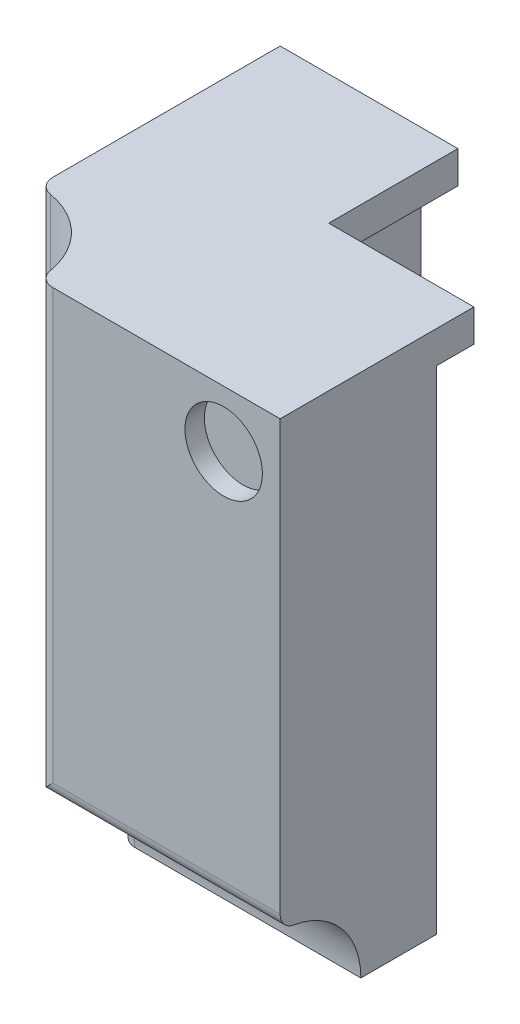
SolidWorks part; units mm, degrees
ref_plane "Front Plane" through (0, 0, 0) normal (0, 0, 1) x (1, 0, 0)
ref_plane "Top Plane" through (0, 0, 0) normal (0, 1, 0) x (1, 0, 0)
ref_plane "Right Plane" through (0, 0, 0) normal (1, 0, 0) x (0, 0, -1)
sketch "Sketch1" plane through (0, 0, 0) normal (0, 1, 0) x (1, 0, 0)
  line L0 (0, 0) -> (50.8, 0)
  line L1 (50.8, 0) -> (50.8, 24.638)
  line L2 (50.8, 24.638) -> (22.1234, 24.638)
  line L3 (22.1234, 24.638) -> (22.1234, 50.8)
  line L4 (22.1234, 50.8) -> (0, 50.8)
  line L5 (0, 50.8) -> (0, 0)
  dimension "D1" = 50.8
  dimension "D2" = 24.638
  dimension "D3" = 22.1234
  dimension "D4" = 50.8
extrude "Boss-Extrude1" add sketch "Sketch1" along normal blind 82.55 contours L0 L1 L2 L3 L4 L5
sketch "Sketch2" plane through (50.8, 0, 0) normal (1, 0, 0) x (0, 0, -1)
  line L0 (0, 82.55) -> (0, 0) construction
  line L1 (0, 0) -> (24.638, 0) construction
  line L2 (12.7, 0) -> (0, 0)
  line L3 (0, 0) -> (0, 12.7)
  arc A0 (0, 12.7) -> (12.7, 0) centre (0, 0) cw
  dimension "D1" = 12.7
extrude "Cut-Extrude1" cut sketch "Sketch2" against normal blind 76.2 contours A0 L2 L3
sketch "Sketch3" plane through (0, 0, -50.8) normal (0, 0, -1) x (-1, 0, 0)
  line L0 (0, 82.55) -> (0, 0) construction
  line L1 (-22.1234, 0) -> (0, 0) construction
  line L2 (-12.7, 0) -> (0, 0)
  line L3 (0, 0) -> (0, 12.7)
  arc A0 (0, 12.7) -> (-12.7, 0) centre (0, 0) ccw
  dimension "D1" = 12.7
extrude "Cut-Extrude2" cut sketch "Sketch3" against normal blind 76.2 contours A0 L2 L3
fillet "Fillet4" radius 2.54 1 edges at (8.9803, 8.9803, -8.9803)
sketch "Sketch4" plane through (0, 0, -24.638) normal (0, 0, -1) x (-1, 0, 0)
  line L0 (-50.8, 77.47) -> (-22.1234, 77.47)
  line L1 (-50.8, 82.55) -> (-50.8, 0) construction
  line L2 (-22.1234, 82.55) -> (-22.1234, 0) construction
  line L3 (-22.1234, 77.47) -> (-22.1234, 82.55)
  line L4 (-22.1234, 82.55) -> (-50.8, 82.55)
  line L5 (-50.8, 82.55) -> (-50.8, 77.47)
  dimension "D1" = 5.08
sketch "Sketch6" plane through (0, 0, -50.8) normal (0, 0, -1) x (-1, 0, 0)
  line L1 (-2.54, 38.1) -> (-6.35, 38.1)
  line L2 (-2.54, 38.1) -> (-2.54, 50.8)
  line L3 (-2.54, 50.8) -> (-6.35, 50.8)
  line L4 (-6.35, 38.1) -> (-6.35, 50.8)
  line L5 (0, 82.55) -> (0, 12.7) construction
  line L6 (-22.1234, 0) -> (-12.7, 0) construction
  dimension "D1" = 12.7
  dimension "D2" = 3.81
  dimension "D3" = 2.54
  dimension "D4" = 38.1
ref_plane "Plane1" through (0, 38.1, 0) normal (0, 1, 0) x (1, 0, 0)
ref_plane "Plane2" through (0, 31.75, 0) normal (0, 1, 0) x (1, 0, 0)
sketch "Sketch7" plane through (0, 31.75, 0) normal (0, 1, 0) x (1, 0, 0)
  line L0 (22.1234, 50.8) -> (0, 50.8) construction
  line L1 (2.54, 48.26) -> (6.35, 48.26)
  line L2 (2.54, 48.26) -> (2.54, 35.56)
  line L3 (2.54, 35.56) -> (6.35, 35.56)
  line L4 (6.35, 48.26) -> (6.35, 35.56)
  line L5 (0, 50.8) -> (0, 0) construction
  dimension "D1" = 3.81
  dimension "D2" = 12.7
  dimension "D3" = 2.54
  dimension "D4" = 2.54
ref_plane "Plane3" through (6.35, 0, 0) normal (1, 0, 0) x (0, 0, -1)
sketch "Sketch11" plane through (0, 82.55, 0) normal (0, 1, 0) x (1, 0, 0)
  line L0 (0, 50.8) -> (0, 0) construction
  line L1 (0, 0) -> (50.8, 0) construction
  line L2 (0, 12.7) -> (0, 0)
  line L3 (0, 0) -> (12.7, 0)
  arc A0 (0, 12.7) -> (12.7, 0) centre (0, 0) cw
  dimension "D1" = 12.7
extrude "Cut-Extrude5" cut sketch "Sketch11" against normal through all
fillet "Fillet7" radius 2.54 4 edges at (31.75, 12.7, 0) (0, 12.7, -31.75) (0, 47.625, -12.7) (12.7, 47.625, 0)
extrude "Boss-Extrude2" add sketch "Sketch4" along normal blind 5.842 contours L0 L3 L4 L5
sketch "Sketch12" plane through (22.1234, 0, 0) normal (1, 0, 0) x (0, 0, -1)
  line L1 (30.48, 77.47) -> (50.8, 77.47)
  line L2 (30.48, 77.47) -> (30.48, 82.55)
  line L3 (30.48, 82.55) -> (50.8, 82.55)
  line L4 (50.8, 77.47) -> (50.8, 82.55)
extrude "Boss-Extrude3" add sketch "Sketch12" along normal blind 5.842
sketch "Sketch14" plane through (0, 0, 0) normal (0, 0, 1) x (1, 0, 0)
  line L0 (15.0268, 82.55) -> (50.8, 82.55) construction
  line L1 (50.8, 82.55) -> (50.8, 15.0268) construction
  circle A0 centre (41.91, 73.66) radius 6.096
  dimension "D1" = 12.192
  dimension "D2" = 8.89
  dimension "D3" = 8.89
extrude "Cut-Extrude6" cut sketch "Sketch14" against normal blind 3.048
sketch "Sketch15" plane through (0, 0, 0) normal (-1, 0, 0) x (0, 0, 1)
  line L2 (-50.8, 82.55) -> (-50.8, 15.0268) construction
  line L3 (-50.8, 82.55) -> (-15.0268, 82.55) construction
  circle A0 centre (-41.91, 73.66) radius 6.096
  dimension "D1" = 12.192
  dimension "D2" = 8.89
  dimension "D3" = 8.89
extrude "Cut-Extrude7" cut sketch "Sketch15" against normal blind 3.048
sketch "Sketch16" plane through (0, 82.55, 0) normal (0, 1, 0) x (1, 0, 0)
  line L0 (0, 50.8) -> (27.9654, 50.8)
  line L1 (27.9654, 50.8) -> (27.9654, 30.48) construction
  line L2 (27.9654, 50.8) -> (0, 50.8) construction
  line L3 (27.9654, 50.8) -> (27.9654, 30.48)
  line L4 (27.9654, 30.48) -> (50.8, 30.48)
  line L5 (50.8, 30.48) -> (50.8, 0)
  line L6 (50.8, 0) -> (50.8, 2.1167) construction
  line L7 (50.8, 0) -> (50.8, 30.48) construction
  line L8 (50.8, 0) -> (25.5479, 0)
  line L9 (7.5874, 7.4395) -> (7.4395, 7.5874)
  line L10 (0, 25.5479) -> (0, 50.8)
  arc A0 (7.4395, 7.5874) -> (0, 25.5479) centre (25.4, 25.5479) cw
  arc A1 (25.5479, 0) -> (7.5874, 7.4395) centre (25.5479, 25.4) cw
  point P22 (0, 15.0268)
  point P25 (15.0268, 0)
  dimension "D1" = 25.4
